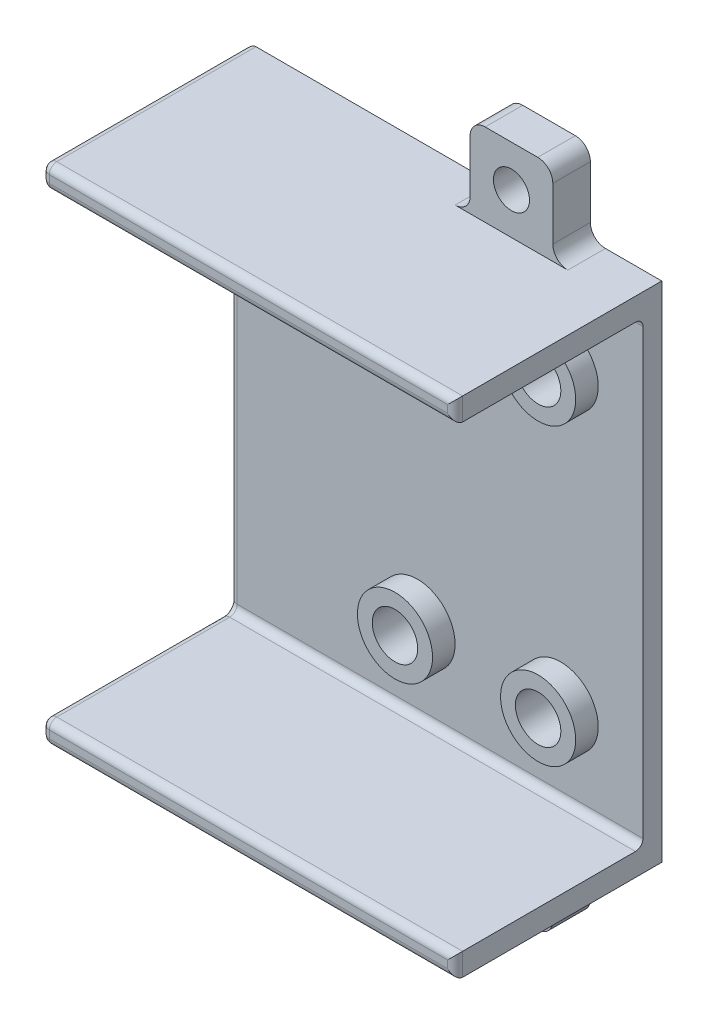
SolidWorks part; units mm, degrees
material "ABS"
ref_plane "X-Y Datum" through (0, 0, 0) normal (0, 0, 1) x (1, 0, 0)
ref_plane "X-Z Datum" through (0, 0, 0) normal (0, 1, 0) x (1, 0, 0)
ref_plane "Y-Z Datum" through (0, 0, 0) normal (1, 0, 0) x (0, 0, -1)
sketch "Sketch1" plane through (0, 0, 0) normal (0, 0, 1) x (1, 0, 0)
  line L1 (-27.5, 33.5) -> (27.5, 33.5)
  line L2 (-27.5, 33.5) -> (-27.5, -33.5)
  line L3 (-27.5, -33.5) -> (27.5, -33.5)
  line L4 (27.5, 33.5) -> (27.5, -33.5)
  line L5 (-27.5, 33.5) -> (27.5, -33.5) construction
  line L6 (-27.5, -33.5) -> (27.5, 33.5) construction
  point P0 (0, 0)
  dimension "D1" = 55
  dimension "D2" = 67
extrude "Boss-Extrude1" add sketch "Sketch1" along normal blind 2.5
sketch "Sketch2" plane through (0, 0, 2.5) normal (0, 0, 1) x (1, 0, 0)
  line L0 (27.5, -33.5) -> (27.5, 33.5) construction
  line L1 (-27.5, 33.5) -> (27.5, 33.5)
  line L2 (-27.5, 33.5) -> (-27.5, 30.5)
  line L3 (-27.5, 30.5) -> (27.5, 30.5)
  line L4 (27.5, 33.5) -> (27.5, 30.5)
  line L5 (-27.5, 33.5) -> (-27.5, -33.5) construction
  line L6 (27.5, -33.5) -> (-27.5, -33.5)
  line L7 (27.5, -33.5) -> (27.5, -30.5)
  line L8 (27.5, -30.5) -> (-27.5, -30.5)
  line L9 (-27.5, -33.5) -> (-27.5, -30.5)
  dimension "D1" = 3
extrude "Boss-Extrude2" add sketch "Sketch2" along normal blind 25
sketch "Sketch3" plane through (0, 0, 2.5) normal (0, 0, 1) x (1, 0, 0)
  circle A0 centre (-2.504, 19.6215) radius 3.025
  circle A1 centre (16.546, 19.6215) radius 3.025
  circle A2 centre (16.546, -19.6215) radius 3.025
  circle A3 centre (-2.504, -19.6215) radius 3.025
  circle A4 centre (-2.504, 19.6215) radius 5
  circle A5 centre (16.546, 19.6215) radius 5
  circle A6 centre (16.546, -19.6215) radius 5
  circle A7 centre (-2.504, -19.6215) radius 5
  dimension "D1" = 6.05
  dimension "D2" = 10
extrude "Boss-Extrude3" add sketch "Sketch3" along normal blind 3
sketch "Sketch4" plane through (0, 0, 2.5) normal (0, 0, 1) x (1, 0, 0)
  circle A0 centre (16.546, -19.6215) radius 3.025 construction
  circle A1 centre (-2.504, -19.6215) radius 3.025 construction
  circle A2 centre (16.546, 19.6215) radius 3.025 construction
  circle A3 centre (-2.504, 19.6215) radius 3.025 construction
  circle A4 centre (16.546, -19.6215) radius 3.025
  circle A5 centre (-2.504, -19.6215) radius 3.025
  circle A6 centre (16.546, 19.6215) radius 3.025
  circle A7 centre (-2.504, 19.6215) radius 3.025
extrude "Cut-Extrude1" cut sketch "Sketch4" against normal blind 2
sketch "Sketch5" plane through (0, 0, 0) normal (0, 0, -1) x (-1, 0, 0)
  line L0 (-27.5, 33.5) -> (27.5, 33.5) construction
  line L1 (-18, 33.5) -> (-7, 33.5)
  line L2 (-18, 33.5) -> (-18, 44.5)
  line L3 (-18, 44.5) -> (-7, 44.5)
  line L4 (-7, 33.5) -> (-7, 44.5)
  line L5 (-12.5, 44.5) -> (-12.5, 33.5)
  line L6 (-27.5, -33.5) -> (-27.5, 33.5) construction
  circle A0 centre (-12.5, 39) radius 2 construction
  line M9 (27.5, 33.5) -> (-27.5, 33.5)
  dimension "D3" = 4
  dimension "D1" = 11
  dimension "D2" = 11
  dimension "D4" = 15
extrude "Boss-Extrude4" add sketch "Sketch5" against normal blind 5 contours L3 L5 L4 M9 | L5 L3 L2 L1 region at (15.25, 39, 0) region at (9.75, 39, 0)
hole_wizard "M4 Clearance Hole1" positions "Sketch8" profile "Sketch7" hole size "M4" standard "ANSI Metric" end condition through all
sketch "Sketch8" plane through (0, 0, 5) normal (0, 0, 1) x (1, 0, 0)
  point P0 (12.5, 39)
sketch "Sketch7" plane through (12.5, 39, 5) normal (1, 0, 0) x (0, -1, 0)
  line L0 (0, 0) -> (0, 5)
  line L1 (0, 5) -> (2.4, 5)
  line L2 (2.4, 5) -> (2.4, 0)
  line L5 (2.4, 0) -> (0, 0)
  line L11 (0, -6.35) -> (0, 107.95) construction
  dimension "Thru Hole Dia." = 4.8
  dimension "Thru Hole Depth" = 5
sketch "Sketch9" plane through (0, 0, 5) normal (0, 0, 1) x (1, 0, 0)
  line L0 (12.5, 41.4) -> (18, 41.4)
  line L1 (12.5, 44.5) -> (12.5, 33.5) construction
  line L2 (18, 33.5) -> (18, 44.5) construction
  line L3 (12.5, 36.6) -> (18, 36.6)
  line L8 (18, 44.5) -> (7, 44.5)
  line L9 (7, 44.5) -> (7, 33.5)
  line L10 (7, 33.5) -> (18, 33.5)
  line L11 (18, 33.5) -> (18, 44.5)
  line L12 (18, 44.5) -> (7, 44.5)
  line L13 (7, 44.5) -> (7, 33.5)
  line L14 (7, 33.5) -> (18, 33.5)
  line L15 (18, 33.5) -> (18, 44.5)
  circle A0 centre (12.5, 39) radius 2.4 construction
  circle A1 centre (12.5, 39) radius 2.4
  circle M5 centre (12.5, 39) radius 2.4
  line M9 (18, 33.5) -> (18, 44.5)
  dimension "D1" = 0
extrude "Cut-Extrude2" [suppressed] cut sketch "Sketch9" against normal through all contours L3 L0 M5 M9
mirror "Mirror2" about plane through (0, 0, 0) normal (0, 1, 0) of "Cut-Extrude2", "M4 Clearance Hole1", "Boss-Extrude4"
fillet "Fillet2" [suppressed] radius 2
fillet "Fillet3" radius 2 8 edges at (18, -33.5, 2.5) (18, -44.5, 2.5) (7, -44.5, 2.5) (7, -33.5, 2.5) (18, 33.5, 2.5) (18, 44.5, 2.5) (7, 44.5, 2.5) (7, 33.5, 2.5)
fillet "Fillet4" radius 1 16 edges at (0, 33.5, 27.5) (27.5, 32, 27.5) (0, 30.5, 27.5) (-27.5, 32, 27.5) (0, -33.5, 27.5) (-27.5, -32, 27.5) (0, -30.5, 27.5) (27.5, -32, 27.5) (0, 30.5, 2.5) (0, -30.5, 2.5) (-27.5, 33.5, 13.75) (-27.5, 30.5, 15) (-27.5, 0, 2.5) (-27.5, -30.5, 15) (-27.5, -33.5, 13.75) (-27.5, 0, 0)
